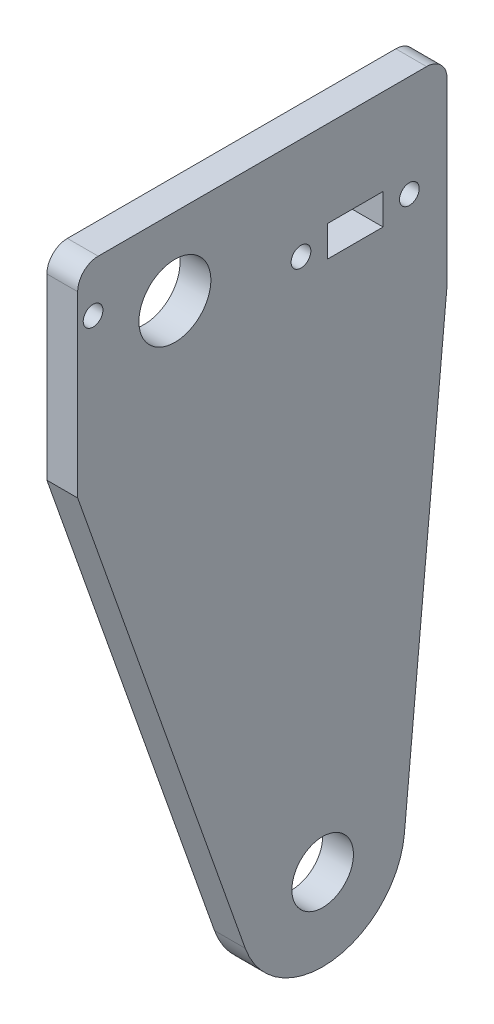
SolidWorks part; units mm, degrees
ref_plane "Front Plane" through (0, 0, 0) normal (0, 0, 1) x (1, 0, 0)
ref_plane "Top Plane" through (0, 0, 0) normal (0, 1, 0) x (1, 0, 0)
ref_plane "Right Plane" through (0, 0, 0) normal (1, 0, 0) x (0, 0, -1)
sketch "Sketch1" plane through (0, 0, 0) normal (1, 0, 0) x (0, 0, -1)
  line L0 (42.1132, 8.7376) -> (42.1132, -18.8943)
  line L1 (-15.0368, 8.7376) -> (-15.0368, -18.8943)
  line L2 (38.9382, 11.9126) -> (-11.8618, 11.9126)
  line L3 (-15.7317, -3.8354) -> (28.7183, -3.8354) construction
  line L4 (-15.0368, -18.8943) -> (10.8885, -92.1946)
  line L5 (42.1132, -18.8943) -> (35.5059, -89.149)
  line L7 (23.5712, -6.2166) -> (32.2072, -6.2166)
  line L8 (23.5712, -6.2166) -> (23.5712, -1.4541)
  line L9 (-9.4805, 9.4615) -> (-9.4805, 0) construction
  line L10 (-12.8841, 9.4615) -> (-9.4805, 9.4615) construction
  line L11 (23.5712, -1.4541) -> (32.2072, -1.4541)
  line L12 (32.2072, -6.2166) -> (32.2072, -1.4541)
  line L13 (23.5712, -6.2166) -> (32.2072, -1.4541) construction
  line L14 (23.5712, -1.4541) -> (32.2072, -6.2166) construction
  circle A0 centre (22.8617, -87.9598) radius 4.7625
  arc A1 (10.8885, -92.1946) -> (35.5059, -89.149) centre (22.8617, -87.9598) ccw
  circle A2 centre (0, 0) radius 5.5626
  circle A3 centre (-12.6555, 4.3307) radius 1.524
  arc A4 (42.1132, 8.7376) -> (38.9382, 11.9126) centre (38.9382, 8.7376) ccw
  circle A5 centre (22.8617, -87.9598) radius 77.47 construction
  circle A6 centre (36.2712, -3.8354) radius 1.524
  arc A10 (-15.0368, 8.7376) -> (-11.8618, 11.9126) centre (-11.8618, 8.7376) cw
  circle A11 centre (19.5072, -3.8354) radius 1.524
  circle A12 centre (2.7432, -3.8354) radius 1.524 [skipped]
  circle A13 centre (-14.0208, -3.8354) radius 1.524 [skipped]
  point P21 (27.8892, -3.8354)
  dimension "D1" = 3.175
  dimension "D2" = 12.7
  dimension "D3" = 154.94
  dimension "D4" = 11.1252
  dimension "D6" = 3.048
  dimension "D9" = 3.048
  dimension "D13" = 5.1308
  dimension "D15" = 9.525
  dimension "D5" = 11.9126
  dimension "D8" = 5.842
  dimension "D10" = 2.3813
  dimension "D11" = 15.748
  dimension "D12" = 5.5562
  dimension "D14" = 57.15
  dimension "D16" = 4.7625
  dimension "D17" = 8.382
  dimension "D18" = 8.636
  dimension "D7" = 2
extrude "Boss-Extrude1" add sketch "Sketch1" along normal blind 4.7625
